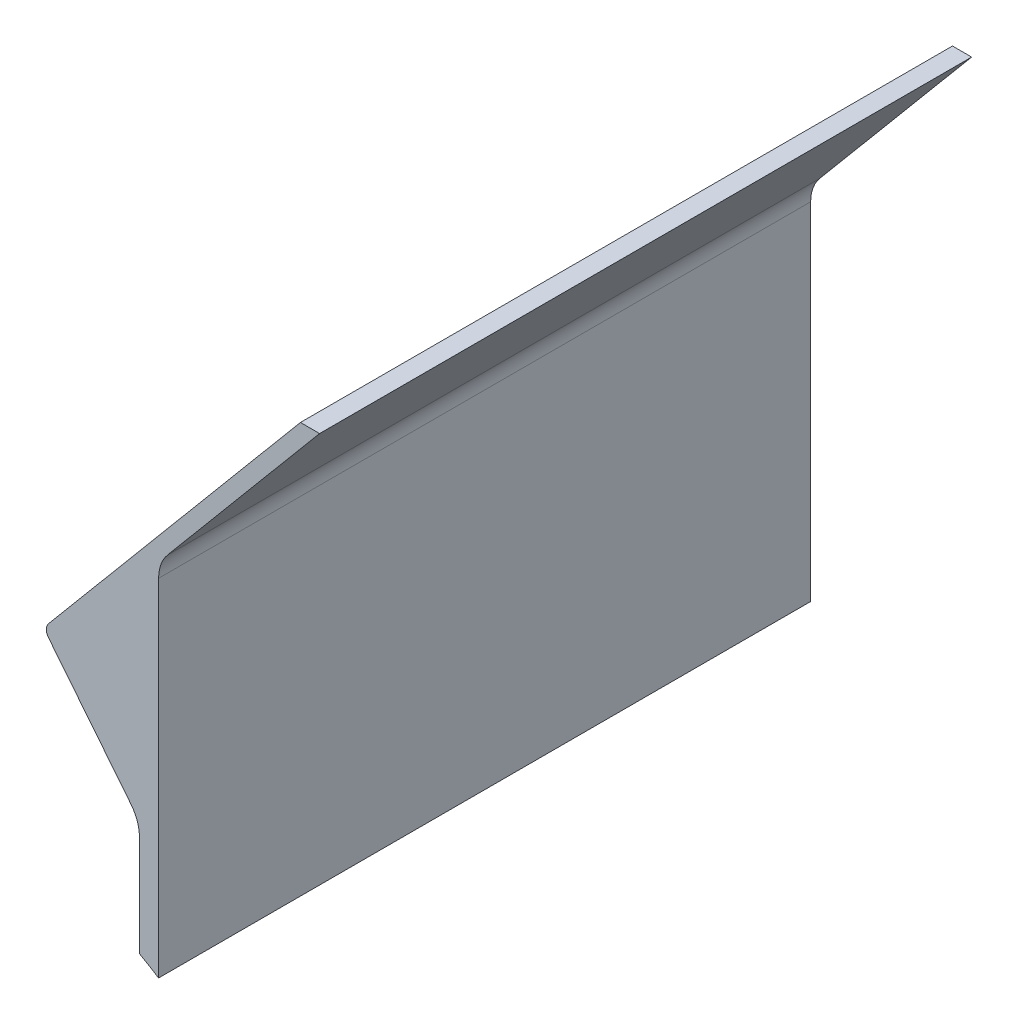
SolidWorks part; units mm, degrees
material "201 Annealed Stainless Steel (SS)"
ref_plane "Front Plane" through (0, 0, 0) normal (0, 0, 1) x (1, 0, 0)
ref_plane "Top Plane" through (0, 0, 0) normal (0, 1, 0) x (1, 0, 0)
ref_plane "Right Plane" through (0, 0, 0) normal (1, 0, 0) x (0, 0, -1)
sketch "Sketch1" plane through (0, 0, 0) normal (0, 0, 1) x (1, 0, 0)
  line L0 (0, 0) -> (0, 93.9)
  line L1 (0, 93.9) -> (41.974, 143.9227)
  line L2 (41.974, 143.9227) -> (36.974, 143.9227)
  line L3 (36.974, 143.9227) -> (-30, 64.1062)
  line L4 (-30, 64.1062) -> (-5, 32.8812)
  line L5 (-5, 32.8812) -> (-5, 3.0096)
  line L7 (-5, 0) -> (-45, 0) construction
  line L8 (-30, 0) -> (-30, 87.9573) construction
  line L9 (-5, 0) -> (-5, -135.5544) construction
  line L10 (-5, -135.5544) -> (-85, -135.5544) construction
  circle A0 centre (-85, -135.5544) radius 160 construction
  arc A1 (0, 0) -> (-5, 3.0096) centre (-85, -135.5544) ccw
  point P15 (-6.3832, 34.4327)
  point P16 (-6.3832, 0)
  point P17 (-6.3832, 0)
  point P18 (-6.3832, 0)
  dimension "D9" = 320
  dimension "D1" = 5
  dimension "D2" = 5
  dimension "D3" = 140
  dimension "D4" = 65.3
  dimension "D5" = 93.9
  dimension "D6" = 40
  dimension "D7" = 25
  dimension "D8" = 40
  dimension "D10" = 80
extrude "Funnel - Right Side" add sketch "Sketch1" along normal blind 170
fillet "Fillet2" radius 10 2 edges at (0, 93.9, 85) (-5, 32.8812, 85)
fillet "Fillet3" radius 2.5 1 edges at (-30, 64.1062, 85)
